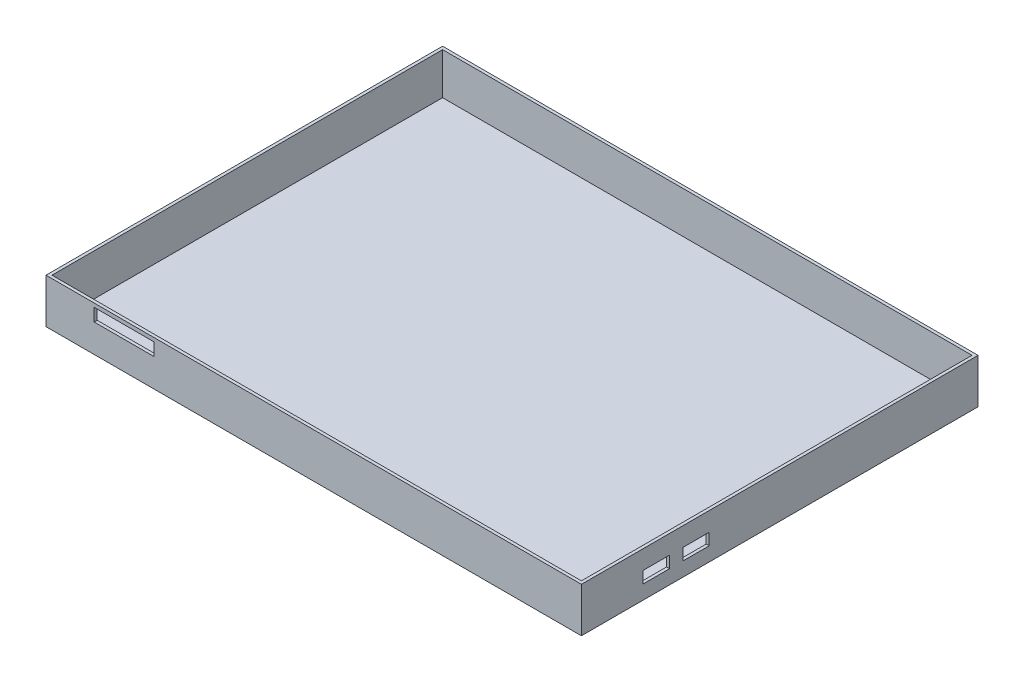
SolidWorks part; units mm, degrees
material "PLA"
ref_plane "Спереди" through (0, 0, 0) normal (0, 0, 1) x (1, 0, 0)
ref_plane "Сверху" through (0, 0, 0) normal (0, 1, 0) x (1, 0, 0)
ref_plane "Справа" through (0, 0, 0) normal (1, 0, 0) x (0, 0, -1)
sketch "Эскиз1" plane through (0, 0, 0) normal (0, 1, 0) x (1, 0, 0)
  line L1 (135, 100) -> (-135, 100)
  line L2 (135, 100) -> (135, -100)
  line L3 (135, -100) -> (-135, -100)
  line L4 (-135, 100) -> (-135, -100)
  line L5 (135, 100) -> (-135, -100) construction
  line L6 (135, -100) -> (-135, 100) construction
  point P0 (0, 0)
  dimension "D1" = 200
  dimension "D2" = 270
extrude "Бобышка-Вытянуть1" add sketch "Эскиз1" along normal blind 1.5
sketch "Эскиз2" plane through (0, 1.5, 0) normal (0, 1, 0) x (1, 0, 0)
  line L0 (133.5, 98.5) -> (-133.5, 98.5)
  line L1 (-133.5, 98.5) -> (-133.5, -98.5)
  line L2 (-133.5, -98.5) -> (-110.7, -98.5)
  line L3 (133.5, -98.5) -> (133.5, 98.5)
  line L4 (-135, 100) -> (-135, -100)
  line L5 (-135, -100) -> (135, -100)
  line L6 (135, -100) -> (135, 100)
  line L7 (135, 100) -> (-135, 100)
  line L8 (-135, 100) -> (-135, -100)
  line L9 (-135, -100) -> (-110.7, -100)
  line L10 (135, -100) -> (135, 100)
  line L11 (135, 100) -> (-135, 100)
  line L12 (-110.7, -98.5) -> (-110.7, -100)
  line L14 (-80.5, -98.5) -> (-80.5, -100)
  line L16 (-80.5, -98.5) -> (133.5, -98.5)
  line L17 (-80.5, -100) -> (135, -100)
  line L18 (-133.5, -98.5) -> (133.5, -98.5) construction
  line L20 (-135, -100) -> (135, -100) construction
  dimension "D3" = 24.3
  dimension "D4" = 54.5
  dimension "D1" = 0
  dimension "D2" = 1.5
extrude "Бобышка-Вытянуть2" add sketch "Эскиз2" along normal offset from surface (21 mm away) 7 offset beyond the face yes
sketch "Эскиз3" plane through (0, 1.5, 0) normal (0, 1, 0) x (1, 0, 0)
  line L1 (-110.7, -98.5) -> (-80.5, -98.5)
  line L2 (-110.7, -98.5) -> (-110.7, -100)
  line L3 (-110.7, -100) -> (-80.5, -100)
  line L4 (-80.5, -98.5) -> (-80.5, -100)
extrude "Бобышка-Вытянуть3" add sketch "Эскиз3" along normal blind 12.7
sketch "Эскиз4" plane through (-110.7, 0, 0) normal (1, 0, 0) x (0, 0, -1)
  line L0 (-100, 22.5) -> (-100, 14.2) construction
  line L1 (-98.5, 22.5) -> (-100, 22.5)
  line L2 (-98.5, 22.5) -> (-98.5, 20.6)
  line L3 (-98.5, 20.6) -> (-100, 20.6)
  line L4 (-100, 22.5) -> (-100, 20.6)
  dimension "D1" = 1.9
extrude "Бобышка-Вытянуть4" add sketch "Эскиз4" along normal up to surface (30.2 mm away) up to face at (-80.5, 18.35, 99.25)
sketch "Эскиз5" plane through (135, 0, 0) normal (1, 0, 0) x (0, 0, -1)
  line L0 (-100, 22.5) -> (-100, 0) construction
  line L1 (-55.55, 13) -> (-68.85, 13)
  line L2 (-55.55, 13) -> (-55.55, 7.1)
  line L3 (-55.55, 7.1) -> (-68.85, 7.1)
  line L4 (-68.85, 13) -> (-68.85, 7.1)
  line L5 (-55.55, 13) -> (-68.85, 7.1) construction
  line L6 (-55.55, 7.1) -> (-68.85, 13) construction
  line L7 (-35.55, 13) -> (-48.85, 13)
  line L8 (-35.55, 13) -> (-35.55, 7.1)
  line L9 (-35.55, 7.1) -> (-48.85, 7.1)
  line L10 (-48.85, 13) -> (-48.85, 7.1)
  line L11 (-35.55, 13) -> (-48.85, 7.1) construction
  line L12 (-35.55, 7.1) -> (-48.85, 13) construction
  line L13 (-100, 0) -> (100, 0) construction
  point P0 (-62.2, 10.05)
  point P5 (-42.2, 10.05)
  dimension "D1" = 13.3
  dimension "D2" = 5.9
  dimension "D3" = 6.7
  dimension "D4" = 31.15
  dimension "D5" = 13
extrude "Вырез-Вытянуть1" cut sketch "Эскиз5" against normal up to surface (1.5 mm away) up to face at (133.5, 12, 0)
